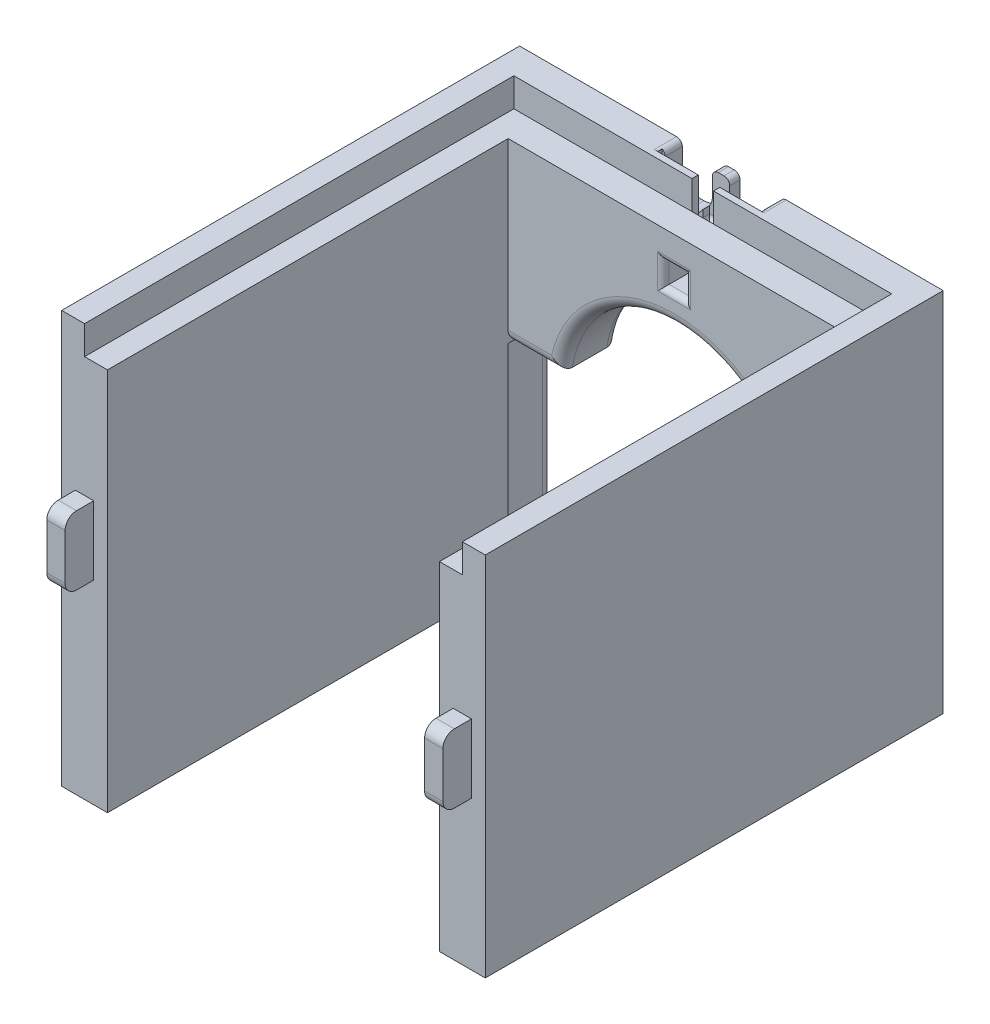
SolidWorks part; units mm, degrees
ref_plane "Front Plane" through (0, 0, 0) normal (0, 0, 1) x (1, 0, 0)
ref_plane "Top Plane" through (0, 0, 0) normal (0, 1, 0) x (1, 0, 0)
ref_plane "Right Plane" through (0, 0, 0) normal (1, 0, 0) x (0, 0, -1)
sketch "Sketch1" plane through (0, 0, 0) normal (0, 0, 1) x (1, 0, 0)
  line L1 (0, 0) -> (185, 0)
  line L2 (0, 0) -> (0, 160)
  line L3 (0, 160) -> (185, 160)
  line L4 (185, 0) -> (185, 160)
  dimension "D1" = 185
  dimension "D2" = 160
extrude "Boss-Extrude1" add sketch "Sketch1" along normal blind 25
sketch "Sketch2" plane through (0, 0, 25) normal (0, 0, 1) x (1, 0, 0)
  line L0 (0, 0) -> (185, 0) construction
  line L1 (0, 160) -> (20, 160)
  line L2 (0, 160) -> (0, 0)
  line L3 (0, 0) -> (20, 0)
  line L4 (20, 160) -> (20, 0)
  line L6 (185, 160) -> (165, 160)
  line L7 (185, 160) -> (185, 0)
  line L8 (185, 0) -> (165, 0)
  line L9 (165, 160) -> (165, 0)
  dimension "D1" = 20
  dimension "D2" = 20
extrude "Boss-Extrude2" add sketch "Sketch2" along normal blind 175
sketch "Sketch5" plane through (0, 0, 0) normal (0, -1, 0) x (1, 0, 0)
  line L0 (0, 0) -> (185, 0) construction
  line L1 (0, 200) -> (20, 200)
  line L2 (0, 200) -> (0, 0)
  line L3 (0, 0) -> (20, 0)
  line L4 (20, 200) -> (20, 0)
extrude "Boss-Extrude3" add sketch "Sketch5" along normal blind 20
sketch "Sketch3" plane through (0, 0, 0) normal (0, 0, -1) x (-1, 0, 0)
  line L0 (-20, 0) -> (-185, 0) construction
  line L1 (-170, 0) -> (-15, 0)
  line L2 (-170, 0) -> (-170, 70)
  line L3 (-170, 70) -> (-141.9343, 70)
  line L4 (-15, 0) -> (-15, 70)
  line L5 (-185, 0) -> (-185, 160) construction
  line L6 (-43.0657, 70) -> (-15, 70)
  arc A0 (-43.0657, 70) -> (-141.9343, 70) centre (-92.5, 62.5) ccw
  dimension "D5" = 100
  dimension "D1" = 15
  dimension "D2" = 70
  dimension "D3" = 155
  dimension "D4" = 7.5
extrude "Cut-Extrude1" cut sketch "Sketch3" against normal blind 25
fillet "Fillet1" [suppressed] radius 5
sketch "Sketch6" plane through (0, 0, 0) normal (0, 1, 0) x (1, 0, 0)
  line L1 (20, -25) -> (15, -25)
  line L2 (20, -25) -> (20, 0)
  line L3 (20, 0) -> (15, 0)
  line L4 (15, -25) -> (15, 0)
extrude "Cut-Extrude2" cut sketch "Sketch6" against normal blind 20
fillet "Fillet2" radius 5 8 edges at (153.4671, 70, 25) (31.5329, 70, 25) (29.0329, 70, 0) (155.9671, 70, 0) (15, 25, 0) (170, 35, 0) (92.5, 112.5, 25) (92.5, 112.5, 0)
sketch "Sketch7" plane through (0, 0, 200) normal (0, 0, 1) x (1, 0, 0)
  line L0 (185, 0) -> (185, 160) construction
  line L1 (171, 65) -> (179, 65)
  line L2 (171, 65) -> (171, 95)
  line L3 (171, 95) -> (179, 95)
  line L4 (179, 65) -> (179, 95)
  line L5 (171, 65) -> (179, 95) construction
  line L6 (171, 95) -> (179, 65) construction
  line L7 (185, 160) -> (165, 160) construction
  point P0 (175, 80)
  dimension "D1" = 8
  dimension "D2" = 30
  dimension "D3" = 10
  dimension "D4" = 65
extrude "Boss-Extrude4" add sketch "Sketch7" along normal blind 12.5
fillet "Fillet3" radius 5 2 edges at (175, 65, 212.5) (175, 95, 212.5)
ref_plane "Plane1" through (92.5, 0, 0) normal (-1, 0, 0) x (0, 0, 1)
mirror "Mirror1" about plane through (92.5, 0, 0) normal (-1, 0, 0) of "Boss-Extrude4", "Fillet3"
sketch "Sketch8" plane through (0, 160, 0) normal (0, 1, 0) x (1, 0, 0)
  line L0 (185, -200) -> (165, -200) construction
  line L1 (175, -200) -> (10, -200)
  line L2 (175, -200) -> (175, -12.5)
  line L3 (175, -12.5) -> (10, -12.5)
  line L4 (10, -200) -> (10, -12.5)
  line L5 (185, 0) -> (0, 0) construction
  dimension "D1" = 165
  dimension "D2" = 12.5
extrude "Cut-Extrude3" cut sketch "Sketch8" against normal blind 12.5
sketch "Sketch10" plane through (0, 0, 0) normal (0, 0, -1) x (-1, 0, 0)
  line L0 (-92.5, 160) -> (-92.5, 122.7003) construction
  line L1 (-185, 160) -> (0, 160) construction
  line L7 (-115.5, 140) -> (-69.5, 160) construction
  line L8 (-115.5, 160) -> (-69.5, 140) construction
  circle A0 centre (-105, 150) radius 8.25
  circle A1 centre (-80, 150) radius 8.25
  point P4 (-92.5, 150)
  dimension "D4" = 16.5
  dimension "D1" = 46
  dimension "D2" = 20
extrude "Cut-Extrude4" cut sketch "Sketch10" against normal blind 7.5
sketch "Sketch11" plane through (0, 160, 0) normal (0, 1, 0) x (1, 0, 0)
  line L0 (92.5, -12.5) -> (92.5, 0) construction
  line L1 (175, -12.5) -> (10, -12.5) construction
  line L2 (185, 0) -> (0, 0) construction
  line L3 (87.5, -7.5) -> (69.75, -7.5)
  line L4 (115.25, -7.5) -> (97.5, -7.5)
  line L5 (115.25, -7.5) -> (115.25, -9.75)
  line L6 (115.25, -9.75) -> (69.75, -9.75)
  line L7 (69.75, -7.5) -> (69.75, -9.75)
  line L8 (115.25, -7.5) -> (69.75, -9.75) construction
  line L9 (115.25, -9.75) -> (69.75, -7.5) construction
  line L10 (97.5, -4.5) -> (87.5, -4.5)
  line L11 (97.5, -4.5) -> (97.5, -7.5)
  line L13 (87.5, -4.5) -> (87.5, -7.5)
  line L14 (97.5, -4.5) -> (87.5, -7.5) construction
  line L15 (97.5, -7.5) -> (87.5, -4.5) construction
  point P6 (92.5, -8.625)
  point P11 (92.5, -6)
  dimension "D1" = 2.25
  dimension "D2" = 45.5
  dimension "D3" = 7.5
  dimension "D4" = 10
  dimension "D5" = 3
extrude "Cut-Extrude5" cut sketch "Sketch11" against normal blind 20
sketch "Sketch12" plane through (0, 160, 0) normal (0, 1, 0) x (1, 0, 0)
  line L0 (185, 0) -> (0, 0) construction
  line L1 (96.2584, 0) -> (113.9472, 0)
  line L2 (96.2584, 0) -> (96.2584, -7.5)
  line L3 (96.2584, -7.5) -> (113.9472, -7.5)
  line L4 (113.9472, 0) -> (113.9472, -7.5)
  line L5 (115.25, -7.5) -> (97.5, -7.5) construction
extrude "Cut-Extrude6" cut sketch "Sketch12" against normal blind 18.25
fillet "Fillet4" radius 8.25 2 edges at (96.2584, 141.75, 2.25) (113.9472, 141.75, 3.75)
mirror "Mirror2" about plane through (92.5, 0, 0) normal (-1, 0, 0) of "Cut-Extrude6", "Fillet4"
sketch "Sketch14" plane through (0, 160, 0) normal (0, 1, 0) x (1, 0, 0)
  line L0 (92.5, -9.75) -> (92.5, -12.25) construction
  line L1 (69.75, -9.75) -> (115.25, -9.75) construction
  line L2 (175, -12.5) -> (10, -12.5) construction
  line L3 (97.1971, -9.5) -> (87.8029, -9.5)
  line L4 (97.1971, -9.5) -> (97.1971, -12.5)
  line L5 (97.1971, -12.5) -> (87.8029, -12.5)
  line L6 (87.8029, -9.5) -> (87.8029, -12.5)
  line L7 (97.1971, -9.5) -> (87.8029, -12.5) construction
  line L8 (97.1971, -12.5) -> (87.8029, -9.5) construction
  point P4 (92.5, -11)
  dimension "D1" = 3
extrude "Cut-Extrude7" cut sketch "Sketch14" against normal blind 35
sketch "Sketch15" plane through (0, 0, 12.5) normal (0, 0, -1) x (-1, 0, 0)
  line L0 (-87.8029, 125) -> (-87.8029, 147.5) construction
  line L1 (-97.1971, 125) -> (-87.8029, 125)
  line L2 (-97.1971, 125) -> (-97.1971, 135)
  line L3 (-97.1971, 135) -> (-87.8029, 135)
  line L4 (-87.8029, 125) -> (-87.8029, 135)
  dimension "D1" = 10
extrude "Cut-Extrude8" cut sketch "Sketch15" against normal blind 30
fillet "Fillet5" radius 2.5 16 edges at (87.5, 140, 6) (92.5, 140, 4.5) (97.5, 140, 6) (69.75, 160, 8.625) (115.25, 160, 8.625) (114.5986, 160, 7.5) (96.2584, 160, 2.25) (113.9472, 160, 3.75) (70.4014, 160, 7.5) (88.7416, 160, 2.25) (71.0528, 160, 3.75) (92.5, 125, 9.5) (97.1971, 130, 25) (92.5, 135, 25) (87.8029, 130, 25) (92.5, 125, 25)
